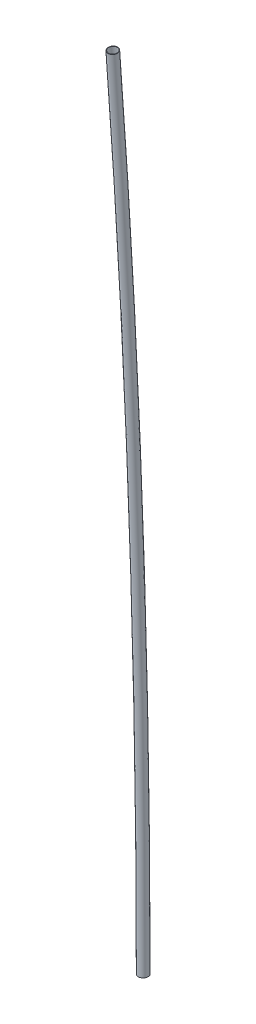
SolidWorks part; units mm, degrees
ref_plane "Спереди" through (0, 0, 0) normal (0, 0, 1) x (1, 0, 0)
ref_plane "Сверху" through (0, 0, 0) normal (0, 1, 0) x (1, 0, 0)
ref_plane "Справа" through (0, 0, 0) normal (1, 0, 0) x (0, 0, -1)
sketch "Эскиз1" plane through (0, 0, 0) normal (0, 1, 0) x (1, 0, 0)
  circle A0 centre (0, 0) radius 40
  dimension "D1" = 80
sketch "Эскиз3" plane through (0, 0, 0) normal (1, 0, 0) x (0, 0, -1)
  line L0 (0, 0) -> (0, 6700) construction
  line L1 (0, 6700) -> (-250, 6700) construction
  arc A0 (0, 0) -> (-250, 6700) centre (-89905, 0) ccw
  dimension "D1" = 6700
  dimension "D2" = 250
sweep "По траектории-Тонкостенный1" add profiles "Эскиз1" path "Эскиз3" parameters "D1"=3
